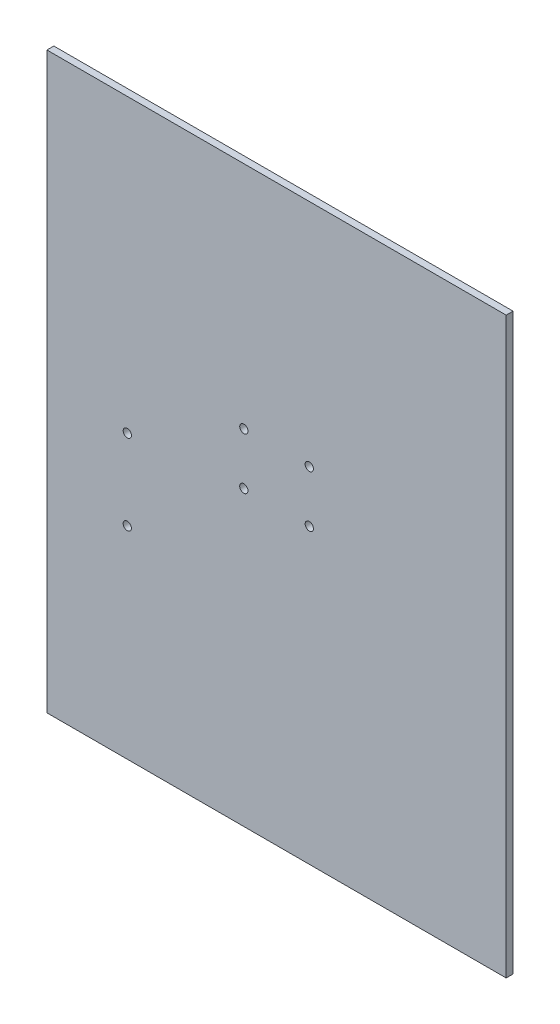
SolidWorks part; units mm, degrees
material "Balsa"
ref_plane "Plano frontal" through (0, 0, 0) normal (0, 0, 1) x (1, 0, 0)
ref_plane "Plano superior" through (0, 0, 0) normal (0, 1, 0) x (1, 0, 0)
ref_plane "Plano direito" through (0, 0, 0) normal (1, 0, 0) x (0, 0, -1)
sketch "Esboço1" plane through (0, 0, 0) normal (0, 0, 1) x (1, 0, 0)
  line L0 (-100, 125) -> (100, 125)
  line L1 (0, 0) -> (0, 9.786) construction
  line L2 (-100, 125) -> (-100, -125)
  line L4 (100, 125) -> (100, -125)
  line L5 (-100, 125) -> (100, -125) construction
  line L6 (-100, -125) -> (100, 125) construction
  line L11 (-100, -125) -> (100, -125)
  line L13 (-14.25, 25) -> (14.25, 25) construction
  circle A0 centre (-14.25, 25) radius 1.8
  circle A1 centre (14.25, 25) radius 1.8
  circle A2 centre (14.25, 2.5) radius 1.8
  circle A3 centre (-14.25, 2.5) radius 1.8
  circle A4 centre (-65, -2) radius 1.8
  circle A5 centre (-65, -37) radius 1.8
  point P0 (0, 0)
  point P6 (0, -16.4394)
  point P7 (0, 125)
  point P15 (0, 25)
  dimension "D6" = 3.6
  dimension "D9" = 35
  dimension "D11" = 3.6
  dimension "D1" = 200
  dimension "D2" = 250
  dimension "D5" = 100
  dimension "D7" = 28.5
  dimension "D8" = 22.5
  dimension "D10" = 123
  dimension "D12" = 35
  dimension "D3" = 2
  dimension "D4" = 2
extrude "Ressalto-extrusão1" add sketch "Esboço1" along normal blind 3
